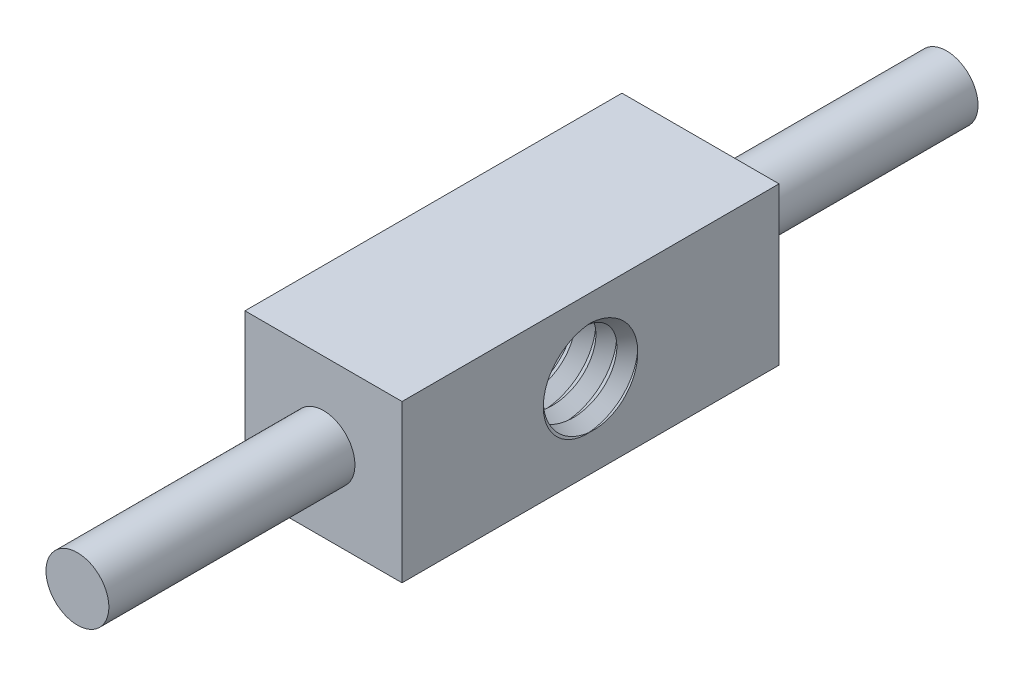
SolidWorks part; units mm, degrees
ref_plane "Front Plane" through (0, 0, 0) normal (0, 0, 1) x (1, 0, 0)
ref_plane "Top Plane" through (0, 0, 0) normal (0, 1, 0) x (1, 0, 0)
ref_plane "Right Plane" through (0, 0, 0) normal (1, 0, 0) x (0, 0, -1)
sketch "Sketch1" plane through (0, 0, 0) normal (0, 0, 1) x (1, 0, 0)
  line L1 (-52.6086, 27.2858) -> (47.3914, 27.2858)
  line L2 (-52.6086, 27.2858) -> (-52.6086, -72.7142)
  line L3 (-52.6086, -72.7142) -> (47.3914, -72.7142)
  line L4 (47.3914, 27.2858) -> (47.3914, -72.7142)
sketch "Sketch2" plane through (0, 0, 0) normal (0, 0, 1) x (1, 0, 0)
  line L0 (-52.6086, 77.2858) -> (97.3914, 77.2858)
  line L1 (-52.6086, 77.2858) -> (-52.6086, -72.7142)
  line L2 (-52.6086, -72.7142) -> (97.3914, -72.7142)
  line L3 (97.3914, 77.2858) -> (97.3914, -72.7142)
extrude "Boss-Extrude1" add sketch "Sketch2" along normal blind 180
sketch "Sketch3" plane through (0, 0, 180) normal (0, 0, 1) x (1, 0, 0)
  line L0 (97.3914, 77.2858) -> (-52.6086, -72.7142) construction
  circle A0 centre (22.3914, 2.2858) radius 30
sketch "Sketch4" plane through (0, 0, 180) normal (0, 0, 1) x (1, 0, 0)
sketch "Sketch5" plane through (0, 0, 180) normal (0, 0, 1) x (1, 0, 0)
  circle A0 centre (22.3914, 2.2858) radius 30
extrude "Boss-Extrude3" add sketch "Sketch5" along normal blind 235
mirror "Mirror1" about plane through (0, 0, 0) normal (0, 0, 1) of "Boss-Extrude3", "Boss-Extrude1"
sketch "Sketch6" plane through (97.3914, 0, 0) normal (1, 0, 0) x (0, 0, -1)
  line L0 (0, 77.2858) -> (0, -72.7142) construction
  line L1 (-180, 77.2858) -> (180, 77.2858) construction
  line L2 (-180, -72.7142) -> (180, -72.7142) construction
  circle A0 centre (0, 2.2858) radius 50
sketch "Sketch7" plane through (97.3914, 0, 0) normal (1, 0, 0) x (0, 0, -1)
  circle A0 centre (0, 2.2858) radius 50
extrude "Cut-Extrude1" cut sketch "Sketch7" against normal through all
sketch "Sketch8" plane through (97.3914, 0, 0) normal (1, 0, 0) x (0, 0, -1)
  circle A0 centre (0, 2.2858) radius 40
  circle A1 centre (0, 2.2858) radius 50
sketch "Sketch9" plane through (97.3914, 0, 0) normal (1, 0, 0) x (0, 0, -1)
  circle A0 centre (0, 2.2858) radius 40
  circle A1 centre (0, 2.2858) radius 50
extrude "Boss-Extrude4" add sketch "Sketch9" against normal through all
sketch "Sketch10" plane through (97.3914, 0, 0) normal (1, 0, 0) x (0, 0, -1)
  circle A0 centre (0, 2.2858) radius 40
curve "Helix/Spiral1" pitch 20 height 220 turns 11
ref_plane "Plane2" through (0, 0, 0) normal (0, 0, -1) x (-1, 0, 0)
sketch "Sketch13" plane through (0, 0, 0) normal (0, 0, -1) x (-1, 0, 0)
  line L0 (112.6086, 42.2858) -> (112.6086, 38.8277)
  line L1 (112.6086, 38.8277) -> (132.6086, 38.8277)
  line L2 (122.6086, 52.2858) -> (112.6086, 42.2858)
  line L3 (122.6086, 52.2858) -> (132.6086, 42.2858)
  line L5 (132.6086, 38.8277) -> (132.6086, 42.2858)
sweep "Cut-Sweep2" cut profiles "Sketch13" path "Helix/Spiral1"
